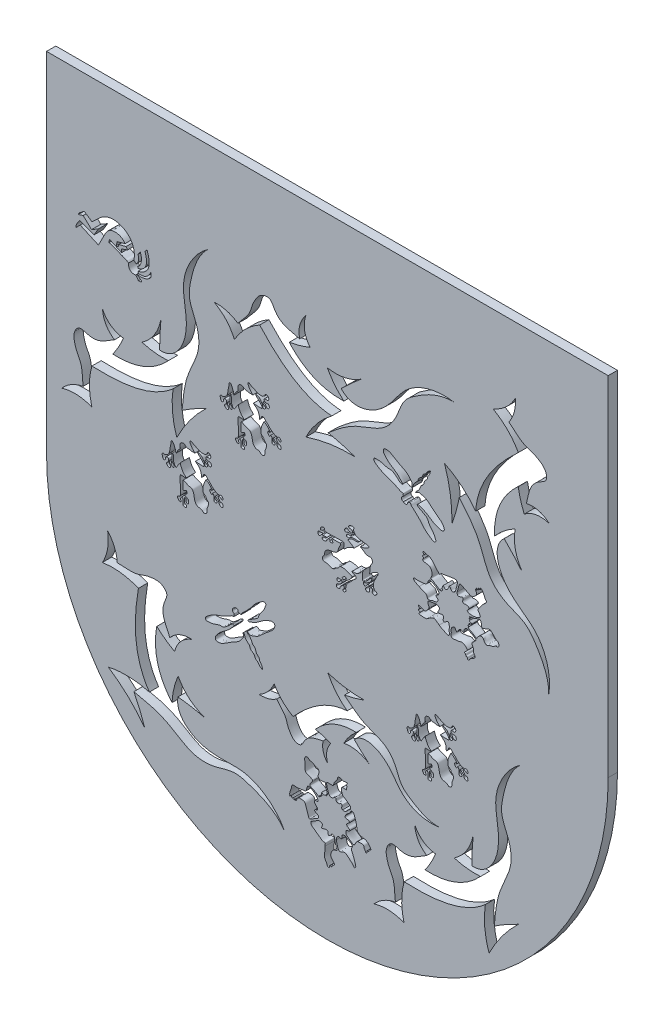
SolidWorks part; units mm, degrees
material "Copper"
ref_plane "Front Plane" through (0, 0, 0) normal (0, 0, 1) x (1, 0, 0)
ref_plane "Top Plane" through (0, 0, 0) normal (0, 1, 0) x (1, 0, 0)
ref_plane "Right Plane" through (0, 0, 0) normal (1, 0, 0) x (0, 0, -1)
sketch "Model" plane through (0, 0, 0) normal (0, 0, 1) x (1, 0, 0)
  line L0 (394.0684, 740.7693) -> (398.6622, 741.3007)
  line L1 (411.6033, 754.0999) -> (411.2957, 759.9449)
  line L2 (405.9947, 783.1893) -> (403.0277, 779.9921)
  line L3 (396.5413, 775.912) -> (393.612, 771.8318)
  line L4 (340.3525, 788.0832) -> (330.4887, 778.9239)
  line L5 (330.4887, 778.9239) -> (319.9202, 785.9695)
  line L6 (311.9939, 778.2193) -> (318.5111, 780.333)
  line L7 (318.5111, 780.333) -> (329.9602, 769.2361)
  line L8 (329.9602, 769.2361) -> (339.2957, 774.7846)
  line L9 (339.2957, 774.7846) -> (333.3069, 764.6565)
  line L10 (333.3069, 764.6565) -> (313.7553, 771.8783)
  line L11 (308.8233, 761.3098) -> (314.4598, 766.9463)
  line L12 (314.4598, 766.9463) -> (339.2957, 755.6733)
  line L13 (339.2957, 755.6733) -> (349.1596, 774.6965)
  line L14 (375.8731, 775.6248) -> (366.0551, 772.786)
  line L15 (366.0551, 772.786) -> (364.9693, 772.786)
  line L16 (364.9693, 772.786) -> (363.6861, 766.9148)
  line L17 (363.6861, 766.9148) -> (366.9435, 767.357)
  line L18 (366.9435, 767.357) -> (366.9435, 770.1209)
  line L19 (366.9435, 770.1209) -> (377.2091, 772.8847)
  line L20 (379.0674, 769.6274) -> (371.0063, 766.9201)
  line L21 (371.0063, 766.9201) -> (371.0063, 762.5101)
  line L22 (1036.7119, 473.4105) -> (1036.7119, 876.6355)
  line L23 (1036.7119, 876.6355) -> (268.3619, 876.6355)
  line L24 (268.3619, 876.6355) -> (268.3619, 473.4105)
  line L25 (268.3619, 473.4105) -> (1036.7119, 473.4105)
  line L26 (1036.7119, 949.6605) -> (268.3619, 949.6605)
  line L27 (268.3619, 949.6605) -> (268.3619, 876.6355)
  line L28 (1036.7119, 876.6355) -> (1036.7119, 949.6605)
  line L29 (384.4445, 760.5081) -> (384.0763, 764.4209)
  line L30 (373.0534, 764.4209) -> (373.0534, 761.3098)
  line L31 (380.6639, 766.7648) -> (373.0534, 764.4209)
  arc A0 (394.0684, 740.7693) -> (390.4794, 745.7939) centre (328.1019, 697.4443) ccw
  arc A1 (393.6582, 749.4855) -> (393.792, 752.0044) centre (388.0165, 751.048) ccw
  arc A2 (393.5074, 755.1974) -> (392.9843, 756.9759) centre (386.3581, 754.0608) ccw
  arc A3 (391.15, 759.2775) -> (387.6746, 761.3098) centre (386.3933, 755.1308) ccw
  arc A4 (355.0412, 770.1209) -> (353.7581, 765.7127) centre (362.1342, 765.6655) ccw
  arc A5 (268.3619, 473.4105) -> (1036.7119, 473.4105) centre (652.5369, 473.4105) ccw
  spline S0 degree 3 poles (855.4392, 698.3823) (844.0962, 713.6317) (829.8955, 725.3892) (812.8372, 733.6549) knots 0.499059 0.499059 0.499059 0.499059 0.500898 0.500898 0.500898 0.500898
  spline S1 degree 3 poles (812.8372, 733.6549) (820.1443, 711.971) (823.5036, 689.6775) (822.9151, 666.7744) knots 0.499152 0.499152 0.499152 0.499152 0.500883 0.500883 0.500883 0.500883
  spline S2 degree 3 poles (822.9151, 666.7744) (827.1929, 678.7461) (830.5522, 690.9617) (832.993, 703.4213) knots 0.499528 0.499528 0.499528 0.499528 0.500373 0.500373 0.500373 0.500373
  spline S3 degree 3 poles (832.993, 703.4213) (842.8567, 691.7291) (862.3877, 668.6155) (871.1795, 627.9534) (898.7, 608.5509) (924.1843, 601.4647) (944.6024, 572.4094) (956.0473, 549.3969) (955.3018, 530.723) knots 0 0 0 0 0.209594 0.407161 0.535059 0.647811 0.757164 1 1 1 1
  spline S4 degree 3 poles (955.3018, 530.723) (959.247, 553.081) (949.6397, 592.8274) (909.5343, 616.9495) (884.1807, 645.3373) (881.8843, 674.5952) (894.3988, 685.4119) knots 0 0 0 0 0.38413 0.579872 0.757798 1 1 1 1
  spline S5 degree 3 poles (894.3988, 685.4119) (903.1222, 676.7447) (911.3753, 667.6494) (919.1583, 658.1259) knots 0.499667 0.499667 0.499667 0.499667 0.500357 0.500357 0.500357 0.500357
  spline S6 degree 3 poles (919.1583, 658.1259) (909.7115, 672.6368) (906.5113, 688.1325) (909.5577, 704.6131) knots 0.498782 0.498782 0.498782 0.498782 0.50096 0.50096 0.50096 0.50096
  spline S7 degree 3 poles (909.5577, 704.6131) (898.7173, 698.7235) (889.2851, 691.1441) (881.2612, 681.8748) knots 0.499295 0.499295 0.499295 0.499295 0.500579 0.500579 0.500579 0.500579
  spline S8 degree 3 poles (881.2612, 681.8748) (880.1178, 711.2872) (890.9027, 736.1819) (913.6159, 756.559) knots 0.498607 0.498607 0.498607 0.498607 0.5017 0.5017 0.5017 0.5017
  spline S9 degree 3 poles (913.6159, 756.559) (915.2717, 746.7779) (918.0248, 737.3154) (921.8752, 728.1715) knots 0.499539 0.499539 0.499539 0.499539 0.500465 0.500465 0.500465 0.500465
  spline S10 degree 3 poles (921.8752, 728.1715) (932.2852, 736.1606) (943.8379, 738.0713) (956.5336, 733.9036) knots 0.498968 0.498968 0.498968 0.498968 0.501122 0.501122 0.501122 0.501122
  spline S11 degree 3 poles (956.5336, 733.9036) (954.7099, 735.3256) (951.1726, 738.0839) (945.2411, 741.017) (939.6264, 742.6548) (934.4156, 743.2451) (929.6214, 743.1617) (926.4462, 742.5859) (924.8297, 742.2928) knots 0 0 0 0 0.203388 0.39451 0.579193 0.715969 0.855401 1 1 1 1
  spline S12 degree 3 poles (924.8297, 742.2928) (925.2108, 743.9218) (925.9826, 747.2202) (927.0309, 752.2207) (928.2759, 757.2089) (929.8877, 762.0557) (932.086, 766.6244) (935.0687, 770.7347) (938.8128, 774.3246) (943.2648, 777.2307) (947.2495, 779.1869) (950.0336, 781.221) (951.6354, 783.0935) (952.4266, 785.453) (952.4919, 788.0258) (952.0106, 790.665) (950.9333, 793.6197) (949.0377, 796.6208) (946.2534, 799.3631) (943.1133, 801.6154) (939.8141, 803.6068) (936.0948, 805.6323) (931.8073, 807.3916) (926.9842, 808.724) (922.1346, 810.4238) (917.5776, 813.0967) (913.2676, 816.3775) (909.1576, 819.9296) (905.1531, 823.5131) (902.3343, 825.6737) (900.9463, 826.7376) knots 0 0 0 0 0.040845 0.082703 0.124739 0.166308 0.207219 0.248003 0.289628 0.333122 0.377274 0.397765 0.416986 0.436378 0.457206 0.479228 0.50152 0.533648 0.564945 0.596348 0.6278 0.659003 0.69968 0.740565 0.781182 0.824711 0.868856 0.913321 0.957319 1 1 1 1
  spline S13 degree 3 poles (900.9463, 826.7376) (907.5632, 836.5492) (910.5256, 847.3969) (909.8334, 859.2808) knots 0.49918 0.49918 0.49918 0.49918 0.500868 0.500868 0.500868 0.500868
  spline S14 degree 3 poles (909.8334, 859.2808) (908.6341, 857.2268) (906.2655, 853.1703) (901.9409, 847.6655) (897.114, 842.7179) (891.7216, 838.3785) (885.8044, 834.5853) (881.5215, 832.6097) (879.3527, 831.6094) knots 0 0 0 0 0.169882 0.335521 0.498998 0.66311 0.829409 1 1 1 1
  spline S15 degree 3 poles (879.3527, 831.6094) (882.0694, 829.9485) (887.4469, 826.6609) (894.7986, 820.7931) (901.7608, 814.0075) (908.268, 806.1584) (911.9399, 800.1017) (913.7887, 797.0524) knots 0 0 0 0 0.193344 0.382711 0.570056 0.783538 1 1 1 1
  spline S16 degree 3 poles (913.7887, 797.0524) (910.619, 794.0802) (904.2416, 788.1003) (895.0787, 778.652) (886.3475, 768.7204) (878.2763, 758.2589) (871.5736, 748.0303) (866.2116, 738.1574) (862.0571, 728.7535) (858.7914, 718.9792) (856.4164, 708.8317) (855.7669, 701.8861) (855.4392, 698.3823) knots 0 0 0 0 0.110893 0.223118 0.335793 0.448248 0.560094 0.647529 0.734746 0.822127 0.91027 1 1 1 1
  spline S17 degree 3 poles (756.6024, 660.2599) (757.4442, 658.4893) (759.5384, 658.5917) (762.3839, 659.8688) (761.7323, 662.8146) (764.2039, 662.7174) (765.6369, 664.0239) (766.6866, 662.6071) (767.1292, 661.035) (768.9106, 659.5483) (771.2993, 657.7826) (773.8896, 654.83) (777.6219, 651.6904) (781.5661, 647.3356) (785.5439, 641.945) (791.2318, 637.7858) (795.5115, 634.7069) (799.4173, 633.3718) (801.4565, 635.418) (800.0957, 638.4359) (798.7207, 642.4097) (794.9624, 647.5334) (791.0103, 651.6568) (789.9314, 656.7955) (785.4827, 659.5707) (780.766, 662.3219) (776.5441, 663.9677) (775.2782, 666.1146) (775.8208, 666.9193) (777.5905, 667.0647) (780.5999, 665.4389) (786.4303, 663.6771) (792.2426, 659.472) (798.1581, 655.3952) (803.6831, 653.3464) (808.1994, 651.6543) (813.1734, 653.262) (811.4897, 660.3783) (804.5383, 665.7458) (795.4754, 672.3131) (788.1882, 679.6452) (781.8398, 680.7151) (778.7291, 682.174) (776.8349, 681.201) (775.1113, 680.5009) (773.9395, 679.3076) (773.1712, 680.0291) knots 0 0 0 0 0.02287 0.030865 0.04383 0.054018 0.062408 0.066972 0.07723 0.088489 0.101131 0.12365 0.148576 0.176512 0.214248 0.251712 0.283384 0.298902 0.308283 0.320402 0.344404 0.375944 0.416788 0.430571 0.453913 0.492135 0.517426 0.52282 0.525816 0.530648 0.548151 0.577862 0.624379 0.657702 0.688663 0.714771 0.732789 0.754604 0.805683 0.870033 0.929204 0.957011 0.969976 0.978366 0.988029 1 1 1 1
  spline S18 degree 3 poles (773.1712, 680.0291) (773.7761, 681.0069) (775.1477, 682.3312) (777.4712, 683.8391) (778.4569, 686.3007) (779.8759, 688.4599) (780.3679, 691.3235) (782.6912, 692.5396) (783.9106, 694.2598) (784.7953, 695.9749) (784.8866, 697.7485) (785.6712, 699.7386) (787.2467, 701.1409) (788.7646, 702.7296) (789.7929, 704.6153) (789.5411, 706.6868) (791.0166, 707.9481) (791.7151, 709.6143) (793.1293, 711.8484) (793.2499, 713.9041) (793.4418, 715.1319) knots 0 0 0 0 0.081648 0.138277 0.193791 0.266989 0.326448 0.389297 0.442066 0.477662 0.526585 0.568162 0.62821 0.675755 0.727172 0.778514 0.811129 0.858756 0.908235 1 1 1 1
  spline S19 degree 3 poles (793.4418, 715.1319) (792.3781, 714.4894) (790.5211, 713.5994) (788.9888, 711.4447) (787.7111, 710.1674) (787.1023, 708.3242) (785.0897, 707.773) (783.7336, 706.1073) (782.8379, 704.1008) (782.1365, 702.1117) (780.5916, 700.632) (778.9846, 699.876) (777.7322, 698.4079) (776.6016, 696.628) (776.3557, 694.0172) (773.8915, 692.4776) (772.4304, 690.3467) (770.5252, 688.5024) (770.0092, 685.781) (769.3028, 684.0101) (768.6269, 683.0801) knots 0 0 0 0 0.091765 0.141244 0.188871 0.221486 0.272828 0.324245 0.37179 0.431838 0.473415 0.522338 0.557934 0.610703 0.673552 0.733011 0.806209 0.861723 0.918352 1 1 1 1
  spline S20 degree 3 poles (768.6269, 683.0801) (767.6682, 683.518) (768.3289, 685.0544) (768.3244, 686.9147) (768.5077, 689.0363) (765.9798, 691.3631) (762.5859, 696.8338) (753.0407, 700.8025) (743.531, 706.7043) (735.9312, 711.1061) (728.7072, 709.9701) (729.1024, 704.7577) (732.3784, 701.2183) (736.3665, 696.8803) (742.3795, 692.9487) (748.4722, 689.1611) (752.3101, 684.4318) (754.9544, 682.262) (755.4898, 680.5689) (754.9504, 679.762) (752.484, 680.1209) (749.3623, 683.4054) (745.0301, 686.7294) (740.7773, 689.7962) (735.6126, 688.8492) (730.2998, 690.9459) (724.1347, 692.4846) (719.9361, 692.2527) (716.6276, 692.3696) (715.5058, 689.7075) (718.2203, 686.5979) (722.6904, 683.8026) (728.6934, 680.1128) (735.1887, 678.472) (740.7126, 676.4702) (745.0316, 674.2044) (748.7451, 672.9248) (751.2837, 671.3824) (753.3342, 670.2965) (754.9569, 670.4821) (756.6656, 670.0469) (755.999, 668.226) (757.0246, 665.9752) (754.0515, 665.4629) (753.9468, 662.3458) (754.6448, 660.3687) (756.6024, 660.2599) knots 0 0 0 0 0.011971 0.021634 0.030024 0.042989 0.070796 0.129967 0.194317 0.245396 0.267211 0.285229 0.311337 0.342298 0.375621 0.422138 0.451849 0.469352 0.474184 0.47718 0.482574 0.507865 0.546087 0.569429 0.583212 0.624056 0.655596 0.679598 0.691717 0.701098 0.716616 0.748288 0.785752 0.823488 0.851424 0.87635 0.898869 0.911511 0.92277 0.933028 0.937592 0.945982 0.95617 0.969135 0.97713 1 1 1 1
  spline S21 degree 3 poles (658.5699, 712.8419) (643.3206, 701.4989) (631.5631, 687.2982) (623.2974, 670.2399) knots 0.499059 0.499059 0.499059 0.499059 0.500898 0.500898 0.500898 0.500898
  spline S22 degree 3 poles (623.2974, 670.2399) (644.9813, 677.547) (667.2748, 680.9063) (690.1779, 680.3178) knots 0.499152 0.499152 0.499152 0.499152 0.500883 0.500883 0.500883 0.500883
  spline S23 degree 3 poles (690.1779, 680.3178) (678.2062, 684.5956) (665.9906, 687.9549) (653.531, 690.3957) knots 0.499528 0.499528 0.499528 0.499528 0.500373 0.500373 0.500373 0.500373
  spline S24 degree 3 poles (653.531, 690.3957) (656.1423, 692.5989) (661.3722, 697.0115) (669.3833, 703.4369) (677.7209, 709.4504) (686.5083, 714.842) (695.8874, 719.2513) (704.5574, 722.4953) (712.1499, 725.3776) (718.5366, 728.07) (724.65, 731.1935) (730.3589, 734.9691) (735.4621, 739.5796) (739.9608, 744.8742) (743.7233, 750.4967) (746.8377, 756.2582) (749.341, 762.0276) (751.6091, 767.8377) (754.0081, 773.5058) (756.863, 778.8483) (760.5568, 783.5978) (764.9376, 787.7418) (769.786, 791.4735) (775.4282, 795.244) (781.694, 799.1541) (788.5929, 803.07) (795.6476, 806.508) (802.9052, 809.3493) (810.415, 811.4344) (818.2268, 812.7189) (823.5362, 812.7094) (826.2293, 812.7045) knots 0 0 0 0 0.046441 0.093012 0.139556 0.186098 0.232927 0.280164 0.3119 0.343319 0.37433 0.405095 0.436065 0.46748 0.499304 0.527852 0.556385 0.584728 0.612637 0.640026 0.666802 0.694016 0.721781 0.749874 0.786231 0.822159 0.857651 0.892821 0.927937 0.963448 1 1 1 1
  spline S25 degree 3 poles (826.2293, 812.7045) (823.4553, 813.0974) (817.8573, 813.8902) (809.3, 813.9009) (800.6934, 813.0911) (792.1628, 811.3806) (783.8539, 808.8044) (775.9065, 805.365) (768.4659, 801.07) (761.8964, 796.1052) (756.2841, 790.5473) (751.4068, 784.71) (746.7988, 778.6126) (742.223, 772.4493) (737.4648, 766.4609) (732.3281, 760.856) (726.7781, 755.7373) (720.732, 751.199) (714.6876, 747.6911) (708.8052, 745.1357) (703.2523, 743.4009) (697.5681, 742.3526) (692.233, 742.1256) (687.3628, 742.6438) (682.9952, 743.7799) (678.8296, 745.653) (674.8858, 748.283) (672.6764, 750.6068) (671.5404, 751.8015) knots 0 0 0 0 0.045817 0.092463 0.139673 0.187153 0.234619 0.281829 0.328618 0.374945 0.416209 0.457635 0.499373 0.541313 0.583303 0.624523 0.665645 0.706728 0.748037 0.779734 0.811541 0.843069 0.874101 0.898603 0.923 0.947648 0.973083 1 1 1 1
  spline S26 degree 3 poles (671.5404, 751.8015) (680.2075, 760.5249) (689.3029, 768.778) (698.8264, 776.561) knots 0.499667 0.499667 0.499667 0.499667 0.500357 0.500357 0.500357 0.500357
  spline S27 degree 3 poles (698.8264, 776.561) (684.3155, 767.1142) (668.8198, 763.914) (652.3392, 766.9604) knots 0.498782 0.498782 0.498782 0.498782 0.50096 0.50096 0.50096 0.50096
  spline S28 degree 3 poles (652.3392, 766.9604) (658.2288, 756.12) (665.8082, 746.6878) (675.0775, 738.6639) knots 0.499295 0.499295 0.499295 0.499295 0.500579 0.500579 0.500579 0.500579
  spline S29 degree 3 poles (675.0775, 738.6639) (645.6651, 737.5205) (620.7703, 748.3054) (600.3933, 771.0186) knots 0.498607 0.498607 0.498607 0.498607 0.5017 0.5017 0.5017 0.5017
  spline S30 degree 3 poles (600.3933, 771.0186) (602.814, 771.4689) (607.6474, 772.3681) (614.7995, 774.2534) (621.8705, 776.5004) (626.4748, 778.351) (628.7808, 779.2779) knots 0 0 0 0 0.249252 0.497679 0.748415 1 1 1 1
  spline S31 degree 3 poles (628.7808, 779.2779) (620.7917, 789.6878) (618.881, 801.2406) (623.0487, 813.9363) knots 0.498968 0.498968 0.498968 0.498968 0.501122 0.501122 0.501122 0.501122
  spline S32 degree 3 poles (623.0487, 813.9363) (614.9554, 804.363) (612.1591, 793.795) (614.6595, 782.2324) knots 0.498846 0.498846 0.498846 0.498846 0.500856 0.500856 0.500856 0.500856
  spline S33 degree 3 poles (614.6595, 782.2324) (606.7878, 784.2083) (592.5669, 785.9568) (580.2246, 798.0668) (575.2316, 811.271) (561.0651, 808.8649) (554.6487, 799.8002) (549.5386, 790.2079) (546.1931, 774.5793) (535.3976, 765.5856) (530.2147, 758.349) knots 0 0 0 0 0.206069 0.324715 0.421259 0.504248 0.61369 0.686644 0.771394 1 1 1 1
  spline S34 degree 3 poles (530.2147, 758.349) (527.8147, 759.825) (523.0765, 762.7389) (516.0019, 765.3322) (509.525, 766.7685) (503.6452, 767.4079) (499.6795, 767.2938) (497.6715, 767.2361) knots 0 0 0 0 0.245664 0.485011 0.653715 0.824659 1 1 1 1
  spline S35 degree 3 poles (497.6715, 767.2361) (510.4233, 760.283) (519.6471, 750.1228) (525.3429, 736.7554) knots 0.499056 0.499056 0.499056 0.499056 0.500947 0.500947 0.500947 0.500947
  spline S36 degree 3 poles (525.3429, 736.7554) (533.8268, 751.5181) (545.3458, 762.9967) (559.8999, 771.1913) knots 0.498959 0.498959 0.498959 0.498959 0.50079 0.50079 0.50079 0.50079
  spline S37 degree 3 poles (559.8999, 771.1913) (585.9574, 742.9265) (618.1758, 715.3276) (658.5699, 712.8419) knots 0 0 0 0 1 1 1 1
  spline S38 degree 3 poles (441.4649, 636.4506) (438.7027, 617.647) (440.4303, 599.2918) (446.6476, 581.385) knots 0.499059 0.499059 0.499059 0.499059 0.500898 0.500898 0.500898 0.500898
  spline S39 degree 3 poles (446.6476, 581.385) (456.8135, 601.8847) (470.202, 620.024) (486.8131, 635.8028) knots 0.499152 0.499152 0.499152 0.499152 0.500883 0.500883 0.500883 0.500883
  spline S40 degree 3 poles (486.8131, 635.8028) (475.323, 630.3624) (464.3098, 624.1) (453.7737, 617.0157) knots 0.499528 0.499528 0.499528 0.499528 0.500373 0.500373 0.500373 0.500373
  spline S41 degree 3 poles (453.7737, 617.0157) (455.0667, 632.258) (457.5999, 662.4122) (480.1356, 697.3815) (474.3954, 730.561) (461.3859, 753.5918) (467.4934, 788.5748) (475.6728, 812.9399) (489.4044, 825.6172) knots 0 0 0 0 0.209594 0.407161 0.535059 0.647811 0.757164 1 1 1 1
  spline S42 degree 3 poles (489.4044, 825.6172) (470.8053, 812.5974) (449.4937, 777.6991) (460.7956, 732.2834) (458.6501, 694.2825) (439.5855, 671.9702) (423.0878, 673.1707) knots 0 0 0 0 0.38413 0.579872 0.757798 1 1 1 1
  spline S43 degree 3 poles (423.0878, 673.1707) (423.0481, 685.4677) (423.6436, 697.7349) (424.8743, 709.9724) knots 0.499667 0.499667 0.499667 0.499667 0.500357 0.500357 0.500357 0.500357
  spline S44 degree 3 poles (424.8743, 709.9724) (424.1161, 706.9165) (422.6299, 700.9266) (418.9513, 692.5387) (414.5869, 685.4467) (409.7146, 679.5434) (404.6059, 674.572) (400.7465, 671.7446) (398.7916, 670.3124) knots 0 0 0 0 0.193794 0.379866 0.561953 0.705377 0.850764 1 1 1 1
  spline S45 degree 3 poles (398.7916, 670.3124) (410.6215, 666.8116) (422.6505, 665.5015) (434.8786, 666.3821) knots 0.499295 0.499295 0.499295 0.499295 0.500579 0.500579 0.500579 0.500579
  spline S46 degree 3 poles (434.8786, 666.3821) (414.8894, 644.7759) (389.6601, 634.7987) (359.1907, 636.4506) knots 0.498607 0.498607 0.498607 0.498607 0.5017 0.5017 0.5017 0.5017
  spline S47 degree 3 poles (359.1907, 636.4506) (360.584, 638.4808) (363.3659, 642.5344) (367.0901, 648.9247) (370.5011, 655.5136) (372.4483, 660.0779) (373.4235, 662.3638) knots 0 0 0 0 0.249252 0.497679 0.748415 1 1 1 1
  spline S48 degree 3 poles (373.4235, 662.3638) (371.4188, 662.7044) (367.5087, 663.3686) (362.0059, 665.411) (356.887, 668.2874) (352.2344, 672.1649) (348.0652, 677.0553) (345.9512, 680.8596) (344.8631, 682.8178) knots 0 0 0 0 0.166107 0.323975 0.477559 0.644562 0.817045 1 1 1 1
  spline S49 degree 3 poles (344.8631, 682.8178) (345.1471, 680.5227) (345.6979, 676.0711) (347.8182, 669.8029) (350.6302, 664.6746) (353.8974, 660.5726) (357.3464, 657.2416) (359.9988, 655.4035) (361.3491, 654.4678) knots 0 0 0 0 0.203388 0.39451 0.579194 0.71597 0.855402 1 1 1 1
  spline S50 degree 3 poles (361.3491, 654.4678) (354.3858, 650.2988) (343.0937, 641.4794) (325.8034, 641.3152) (312.9359, 647.1214) (304.6201, 635.4028) (306.4927, 624.456) (309.6621, 614.0598) (318.3476, 600.6431) (317.0735, 586.65) (318.5257, 577.8681) knots 0 0 0 0 0.206069 0.324715 0.421259 0.504248 0.61369 0.686644 0.771394 1 1 1 1
  spline S51 degree 3 poles (318.5257, 577.8681) (306.909, 575.6092) (297.1438, 570.0334) (289.2301, 561.1407) knots 0.49918 0.49918 0.49918 0.49918 0.500868 0.500868 0.500868 0.500868
  spline S52 degree 3 poles (289.2301, 561.1407) (303.1635, 565.241) (316.87, 564.5789) (330.3497, 559.1543) knots 0.499056 0.499056 0.499056 0.499056 0.500947 0.500947 0.500947 0.500947
  spline S53 degree 3 poles (330.3497, 559.1543) (329.6032, 562.2497) (328.1254, 568.3768) (327.0761, 577.7244) (326.9513, 587.4456) (327.9001, 597.597) (329.5864, 604.4762) (330.4354, 607.9397) knots 0 0 0 0 0.193344 0.382711 0.570057 0.783538 1 1 1 1
  spline S54 degree 3 poles (330.4354, 607.9397) (368.847, 606.3788) (411.1443, 609.6453) (441.4649, 636.4506) knots 0 0 0 0 1 1 1 1
  spline S55 degree 3 poles (398.6622, 741.3007) (398.4257, 741.8358) (397.9684, 742.8701) (396.6946, 743.99) (395.2615, 744.9259) (393.6785, 745.863) (392.8445, 746.8425) (392.4277, 747.332) knots 0 0 0 0 0.196821 0.380507 0.565079 0.782625 1 1 1 1
  spline S56 degree 3 poles (392.4277, 747.332) (399.2913, 746.254) (407.7149, 747.3555) (411.6033, 754.0999) knots 0 0 0 0 1 1 1 1
  spline S57 degree 3 poles (411.2957, 759.9449) (410.0193, 756.305) (405.1809, 749.4227) (397.0049, 749.0541) (393.6582, 749.4855) knots 0 0 0 0 0.533061 1 1 1 1
  spline S58 degree 3 poles (393.792, 752.0044) (399.8073, 752.6889) (412.5827, 762.2294) (407.6953, 777.3765) (405.9947, 783.1893) knots 0 0 0 0 0.47437 1 1 1 1
  spline S59 degree 3 poles (403.0277, 779.9921) (403.402, 778.8189) (404.1766, 776.3908) (405.0075, 772.5986) (405.3487, 768.6633) (404.8914, 764.7443) (403.2433, 761.1564) (400.6031, 758.2529) (397.3086, 756.0479) (394.7671, 755.4792) (393.5074, 755.1974) knots 0 0 0 0 0.119133 0.246548 0.374821 0.49994 0.62392 0.749865 0.876014 1 1 1 1
  spline S60 degree 3 poles (392.9843, 756.9759) (393.7336, 757.5895) (395.2261, 758.8116) (396.7532, 761.3154) (397.744, 764.0691) (398.2748, 767.5514) (398.1262, 771.6448) (397.0621, 774.51) (396.5413, 775.912) knots 0 0 0 0 0.139162 0.277189 0.41746 0.560255 0.784827 1 1 1 1
  spline S61 degree 3 poles (393.612, 771.8318) (393.9197, 770.6136) (394.5424, 768.1486) (394.2735, 764.5943) (393.2166, 761.4417) (391.839, 759.999) (391.15, 759.2775) knots 0 0 0 0 0.277644 0.561767 0.780846 1 1 1 1
  spline S62 degree 3 poles (387.6746, 761.3098) (387.9674, 762.7938) (388.5573, 765.7836) (388.5407, 770.391) (387.8703, 774.958) (386.4658, 779.3532) (384.3136, 783.4167) (381.4366, 786.9964) (377.9965, 790.052) (374.1168, 792.5512) (369.9181, 794.4661) (365.4975, 795.7427) (360.9482, 796.3219) (356.371, 796.1346) (351.8975, 795.1584) (347.6578, 793.4587) (343.7573, 791.0848) (341.4878, 789.0841) (340.3525, 788.0832) knots 0 0 0 0 0.061928 0.124766 0.187869 0.250713 0.313103 0.375422 0.438091 0.501079 0.564057 0.626762 0.689139 0.751391 0.813769 0.876055 0.937996 1 1 1 1
  spline S63 degree 3 poles (319.9202, 785.9695) (318.0889, 785.0168) (316.2963, 782.4975) (312.761, 780.7537) (312.0149, 778.9968) (311.9939, 778.2193) knots 0.000001 0.000001 0.000001 0.000001 0.53037 0.798279 1 1 1 1
  spline S64 degree 3 poles (313.7553, 771.8783) (312.4362, 770.3254) (310.1516, 767.1089) (308.3122, 763.3877) (308.8233, 761.3098) knots 0 0 0 0 0.505243 0.999999 0.999999 0.999999 0.999999
  spline S65 degree 3 poles (349.1596, 774.6965) (349.9011, 775.9058) (351.3362, 778.2462) (354.5494, 780.7914) (358.2183, 782.3143) (362.1943, 782.7617) (366.2139, 782.2665) (370.018, 780.8883) (373.4525, 778.7474) (375.0724, 776.6576) (375.8731, 775.6248) knots 0 0 0 0 0.132212 0.255877 0.377103 0.500628 0.62693 0.753643 0.87824 1 1 1 1
  spline S66 degree 3 poles (377.2091, 772.8847) (377.5634, 772.3865) (378.2914, 771.363) (378.8042, 770.2161) (379.0674, 769.6274) knots 0 0 0 0 0.486685 1 1 1 1
  spline S67 degree 3 poles (371.0063, 762.5101) (369.5145, 763.2202) (366.5307, 764.6403) (362.3428, 766.5443) (358.3615, 768.0656) (356.1482, 769.4356) (355.0412, 770.1209) knots 0 0 0 0 0.279953 0.559931 0.77989 1 1 1 1
  spline S68 degree 3 poles (353.7581, 765.7127) (356.3809, 765.8234) (359.8427, 763.5699) (365.5071, 762.2133) (369.3333, 760.0009) (373.0194, 759.1002) (375.0985, 757.6998) (376.6296, 757.0407) (377.4263, 757.0185) (377.9605, 757.1643) (378.3991, 755.6873) (379.9282, 755.6905) (380.4835, 754.8142) knots 0 0 0 0 0.251875 0.414608 0.592798 0.701894 0.797976 0.851277 0.865807 0.882757 0.897063 1 1 1 1
  spline S69 degree 3 poles (380.4835, 754.8142) (380.425, 753.0287) (380.6606, 749.7379) (384.4215, 745.43) (388.3914, 745.2819) (390.4794, 745.7939) knots 0 0 0 0 0.337832 0.586607 0.999999 0.999999 0.999999 0.999999
  spline S70 degree 3 number of poles 211 (553.5996, 691.043) -> (534.47, 643.1846)
  spline S71 degree 3 number of poles 202 (534.47, 643.1846) -> (553.5996, 691.043)
  spline S72 degree 3 number of poles 211 (717.9194, 548.5843) -> (670.0611, 567.714)
  spline S73 degree 3 number of poles 202 (670.0611, 567.714) -> (717.9194, 548.5843)
  spline S74 degree 3 poles (854.7267, 525.1728) (854.7156, 525.4695) (854.4632, 526.4167) (853.3606, 527.6695) (852.436, 530.1345) (852.647, 533.6418) (851.2938, 536.7161) (849.4872, 540.1347) (852.3065, 541.5707) (853.5083, 543.541) (856.5541, 545.4554) (854.1319, 547.7374) (851.9112, 549.4517) (848.6771, 550.931) (846.0109, 552.4905) (843.8726, 553.0576) (841.9159, 553.113) (840.7583, 551.8324) (839.5128, 550.4813) (839.5436, 548.7276) (839.6793, 547.1841) (838.6204, 545.7358) (837.0104, 546.454) (836.3055, 547.6122) (834.5664, 548.3554) (834.1738, 546.8717) (833.0688, 547.337) (832.8111, 546.2366) (831.9607, 545.8011) (831.4181, 544.9158) (831.4732, 543.8351) (830.6854, 543.1297) (829.5254, 542.0237) (828.9716, 543.4529) (828.0096, 544.0033) (827.9463, 545.2599) (826.82, 546.2532) (825.6144, 546.4648) (825.081, 546.266) knots 0.504555 0.504555 0.504555 0.504555 0.511553 0.525179 0.541676 0.56913 0.600474 0.622434 0.636981 0.659932 0.68115 0.694561 0.720784 0.749249 0.772169 0.789778 0.798757 0.813966 0.825584 0.838885 0.850874 0.860557 0.872175 0.881839 0.894069 0.90074 0.907161 0.912142 0.921202 0.928088 0.934128 0.943867 0.951926 0.961608 0.968252 0.976356 0.986624 1 1 1 1
  spline S75 degree 3 poles (825.081, 546.266) (824.4998, 546.0495) (823.7305, 544.9195) (822.3193, 543.7851) (821.8901, 541.8871) (821.8469, 539.8151) (822.1857, 537.6909) (821.7845, 535.8136) (821.3671, 534.0604) (822.493, 532.7637) (824.2336, 531.5046) (827.2223, 532.3885) (831.1377, 532.1012) (834.4417, 533.5727) (837.7608, 533.8058) (840.074, 532.4883) (842.3443, 531.1175) (843.468, 529.6086) (844.4128, 528.4367) (843.5314, 526.8832) (842.0145, 525.7417) (840.8922, 524.5416) (839.2329, 523.1152) (840.8874, 523.0239) (841.6949, 522.2627) (841.953, 521.2899) (841.9054, 519.8912) (843.2697, 520.2253) (844.2039, 519.3409) (844.0106, 518.157) (844.7009, 516.9367) (845.9969, 517.1891) (846.9815, 518.145) (847.9344, 520.2842) (850.9746, 522.0123) (854.7878, 523.5288) (854.7267, 525.1728) knots 0 0 0 0 0.014572 0.027691 0.040062 0.056022 0.074575 0.087095 0.099487 0.112049 0.122469 0.146161 0.17505 0.210779 0.224879 0.247648 0.268501 0.283047 0.291262 0.298282 0.318986 0.332278 0.342017 0.350665 0.356735 0.367003 0.373536 0.381751 0.390229 0.397964 0.407796 0.415531 0.423406 0.438251 0.465786 0.504555 0.504555 0.504555 0.504555
  spline S76 degree 3 poles (805.4858, 538.5113) (807.418, 537.1345) (810.9488, 535.4477) (814.8409, 533.4538) (817.1973, 532.4149) (818.7685, 532.7858) (820.1409, 534.3398) (818.3799, 538.565) (819.8616, 542.4462) (819.0596, 545.8953) (818.814, 547.2267) (817.9478, 548.5282) (816.1449, 548.4901) (814.8039, 547.2508) (813.597, 545.9784) (811.9864, 545.7523) (810.7317, 546.913) (811.104, 548.4999) (811.3567, 550.0127) (811.5217, 551.9951) (809.8145, 553.1091) (808.1713, 553.0988) (806.7662, 552.4763) (805.3666, 552.1796) (803.852, 552.831) (804.0968, 554.3975) (804.9768, 555.6358) (805.8578, 557.2216) (805.9885, 559.0447) (804.7162, 560.1008) (803.507, 561.3017) (800.748, 561.2807) (797.5971, 561.1224) (794.1617, 560.033) (791.2299, 560.2158) (790.5035, 559.3337) knots 0.478828 0.478828 0.478828 0.478828 0.529291 0.559899 0.572826 0.581694 0.592367 0.611843 0.667376 0.675309 0.685952 0.69655 0.704336 0.720475 0.733793 0.740048 0.753257 0.761371 0.772727 0.787095 0.798671 0.810811 0.820651 0.830686 0.841572 0.847492 0.860854 0.873938 0.886078 0.89489 0.907337 0.920807 0.950162 0.973962 1 1 1 1
  spline S77 degree 3 poles (790.5035, 559.3337) (790.1092, 558.855) (789.797, 557.3309) (790.5553, 555.2794) (791.6446, 553.2833) (791.3723, 550.6409) (789.2863, 548.5666) (787.7778, 546.1877) (785.319, 545.2623) (783.5488, 545.8324) (782.151, 547.1134) (780.2958, 547.1746) (778.9154, 547.8019) (777.3273, 548.4132) (776.8538, 546.749) (778.1455, 546.043) (779.4238, 544.4564) (777.9379, 543.7264) (777.1106, 543.0125) (777.3271, 542.1146) (778.2039, 541.688) (779.2781, 541.0124) (778.8481, 539.6936) (777.5023, 539.247) (778.4016, 537.9869) (780.0025, 537.2444) (782.3281, 537.5134) (784.8715, 536.7597) (786.7517, 537.3774) (788.6091, 537.2663) (789.8389, 538.5832) (791.8766, 539.6664) (794.0447, 541.5891) (796.4695, 542.2704) (798.5437, 543.0118) (801.7465, 541.7252) (803.742, 539.7539) (805.4858, 538.5113) knots 0 0 0 0 0.014132 0.028091 0.046467 0.061075 0.080327 0.106952 0.118855 0.132814 0.143702 0.158049 0.168937 0.178675 0.185476 0.196149 0.207954 0.217111 0.224753 0.229187 0.233812 0.245219 0.25032 0.260205 0.265741 0.276813 0.297845 0.313053 0.331461 0.338472 0.350851 0.36636 0.387989 0.410457 0.419325 0.433284 0.478828 0.478828 0.478828 0.478828
  spline S78 degree 3 poles (778.0075, 570.5143) (780.0661, 569.5118) (783.1112, 568.048) (786.9751, 566.9334) (788.5696, 565.0707) (788.9651, 563.4449) (789.6815, 561.6764) (791.6698, 561.6643) (794.102, 561.7493) (797.1328, 563.5987) (800.7714, 563.2037) (803.1305, 565.0934) (804.7999, 567.7091) (802.7015, 569.4886) (800.807, 570.8467) (801.8783, 572.6611) (804.0536, 573.0392) (805.9135, 576.4543) (804.1487, 578.8232) (802.9883, 579.9226) knots 0.504834 0.504834 0.504834 0.504834 0.576836 0.611293 0.626896 0.650469 0.665272 0.679879 0.706235 0.743178 0.786027 0.811413 0.836772 0.868093 0.88489 0.900027 0.920088 0.952311 1 1 1 1
  spline S79 degree 3 poles (802.9883, 579.9226) (801.7485, 581.0974) (798.7873, 582.8712) (795.3192, 585.0902) (791.8689, 585.4557) (790.213, 583.1203) (789.9388, 580.3318) (787.3314, 577.7918) (782.7443, 577.1396) (777.6605, 576.9374) (773.7802, 576.8379) (770.2967, 577.9115) (770.6189, 574.4087) (773.7729, 572.5891) (776.3519, 571.3204) (778.0075, 570.5143) knots 0 0 0 0 0.050956 0.110768 0.127692 0.151657 0.1886 0.214928 0.257827 0.32988 0.369733 0.392596 0.414598 0.446931 0.504834 0.504834 0.504834 0.504834
  spline S80 degree 3 poles (869.7038, 597.2402) (869.9989, 597.8317) (870.4527, 599.3857) (868.167, 600.9953) (867.6003, 603.597) (866.229, 605.8706) (865.2271, 607.7388) (864.164, 609.4172) (863.1095, 609.9596) (862.2549, 611.362) (861.8913, 610.0527) (862.1493, 609.3433) (861.5981, 607.9983) (860.5154, 609.2671) (859.2677, 609.4883) (858.8867, 608.5833) (859.0642, 607.8874) (859.172, 606.5394) (857.7751, 607.13) (856.6953, 608.4384) (856.7518, 607.1185) (856.7854, 606.4567) (857.0529, 604.9791) (855.8426, 605.8861) (854.6883, 606.9704) (855.7389, 603.8295) (856.6795, 602.448) (856.6734, 599.0698) (853.8973, 597.2253) (851.7764, 594.6572) (848.3769, 594.5954) (845.3134, 596.5605) (840.7507, 598.8559) (837.1629, 600.6709) (834.0365, 601.8126) (832.5837, 600.0078) (832.1257, 596.6866) (830.9486, 593.0503) (830.0921, 590.6529) (829.979, 589.8896) knots 0.500637 0.500637 0.500637 0.500637 0.512936 0.528576 0.548023 0.564246 0.580318 0.590594 0.601293 0.606635 0.613091 0.617263 0.623516 0.633148 0.640335 0.643714 0.650147 0.655827 0.663715 0.671887 0.676813 0.681738 0.688538 0.695805 0.702304 0.711196 0.735999 0.748354 0.770642 0.796876 0.810528 0.833065 0.867216 0.909936 0.918073 0.925213 0.950202 0.984809 1 1 1 1
  spline S81 degree 3 poles (829.979, 589.8896) (829.8443, 588.9798) (829.9625, 587.4889) (831.3194, 585.8209) (832.8892, 586.1453) (834.6215, 586.5171) (836.1549, 587.0883) (838.1859, 587.677) (838.6328, 585.6977) (837.89, 584.3518) (837.0585, 582.4796) (838.1992, 581.7738) (838.8606, 580.7571) (840.6635, 581.1074) (842.7099, 581.0853) (844.8355, 580.5638) (846.8725, 579.0482) (845.6933, 576.8788) (844.4229, 576.0807) (843.6297, 574.7863) (844.9347, 573.4782) (847.8722, 572.4203) (852.5769, 572.3779) (857.3295, 573.2636) (860.2024, 574.5829) (862.2608, 576.3112) (860.9576, 578.5295) (860.3166, 580.6688) (858.77, 581.8248) (858.5138, 584.3854) (862.0878, 587.7038) (864.5078, 593.1341) (868.8196, 595.4672) (869.7038, 597.2402) knots 0 0 0 0 0.018106 0.028257 0.036995 0.047075 0.063324 0.072245 0.080505 0.094365 0.105835 0.112246 0.118123 0.128259 0.14337 0.159759 0.172047 0.185228 0.198483 0.204335 0.210834 0.22963 0.267209 0.300749 0.323829 0.33024 0.34995 0.362456 0.375908 0.384671 0.409299 0.463774 0.500637 0.500637 0.500637 0.500637
  spline S82 degree 3 poles (887.4973, 555.4028) (887.5101, 556.1322) (886.9135, 557.461) (885.5335, 559.2919) (883.388, 560.0423) (881.9827, 561.7452) (880.1219, 563.5083) (877.971, 565.7797) (874.7629, 568.6649) (871.5198, 566.6262) (868.9448, 565.472) (866.5659, 565.267) (864.7837, 564.1112) (863.7227, 565.5261) (863.0755, 567.0196) (863.3183, 569.3941) (862.6167, 571.4656) (861.0311, 573.301) (859.5218, 572.5685) (853.9638, 570.6648) (852.9872, 570.3395) (848.3924, 569.6691) (846.2383, 569.0194) (848.4835, 568.032) (847.3508, 567.2149) (845.821, 566.4065) (848.2693, 565.4997) (846.198, 564.651) (847.871, 563.5405) (849.0909, 563.3992) (849.9618, 562.0947) (849.8496, 561.7075) knots 0.501862 0.501862 0.501862 0.501862 0.519236 0.534137 0.5552 0.570034 0.585574 0.615241 0.648082 0.669845 0.697056 0.714762 0.727938 0.737827 0.750083 0.767263 0.791499 0.802801 0.815778 0.844541 0.893357 0.9094 0.918529 0.930779 0.935723 0.946666 0.957552 0.965495 0.976801 0.986048 1 1 1 1
  spline S83 degree 3 poles (849.8496, 561.7075) (849.7018, 561.1974) (847.9125, 561.4539) (846.5948, 561.1518) (846.0682, 560.2129) (846.1739, 559.13) (845.5451, 558.2858) (844.4433, 558.0221) (845.2298, 557.1834) (846.0573, 556.0467) (843.7065, 556.0551) (845.8455, 555.0947) (846.6183, 553.7616) (849.3522, 553.1094) (851.3215, 551.5458) (853.2641, 550.2013) (854.8325, 549.4379) (855.7081, 548.4708) (856.7241, 548.1472) (857.3994, 549.0595) (857.6377, 550.3173) (858.7949, 551.2714) (859.7475, 552.4692) (860.7765, 553.6533) (862.6761, 553.9711) (864.6828, 553.8824) (866.2543, 552.2749) (866.6108, 550.4075) (867.8499, 549.1519) (868.9372, 547.9646) (870.6621, 546.7448) (872.4139, 548.2132) (874.3536, 548.4849) (876.0242, 549.4154) (877.9714, 549.666) (879.944, 550.1874) (881.3106, 551.4917) (882.9402, 552.4815) (884.8882, 552.1778) (886.8262, 553.2641) (887.4846, 554.6705) (887.4973, 555.4028) knots 0 0 0 0 0.01838 0.026278 0.032103 0.04171 0.05092 0.055388 0.062762 0.07037 0.079847 0.089138 0.102577 0.122255 0.148304 0.162711 0.17796 0.188649 0.193743 0.2001 0.211512 0.224246 0.233456 0.248306 0.259088 0.277737 0.293277 0.307839 0.321334 0.333343 0.347417 0.364207 0.379373 0.393936 0.408238 0.425613 0.440597 0.452438 0.468989 0.484416 0.501862 0.501862 0.501862 0.501862
  spline S84 degree 3 poles (803.0378, 601.6929) (802.1727, 602.3301) (800.9003, 604.5973) (798.2506, 607.0609) (796.4465, 609.918) (793.8982, 611.9965) (791.2216, 613.3042) (788.0742, 613.4991) (786.153, 614.9175) (783.9238, 615.164) (783.0833, 613.517) (784.225, 612.678) (785.0766, 611.2716) (783.7227, 610.4259) (782.0433, 609.4805) (783.5919, 608.4045) (785.2213, 607.0393) (782.9886, 606.6067) (783.0003, 604.986) (783.0984, 603.0162) (785.6582, 603.2571) (788.1525, 602.4044) (791.2794, 602.6285) (793.6081, 600.5119) (795.2167, 598.0363) (795.8046, 594.7702) (795.814, 591.3475) (793.9864, 589.6456) (793.8377, 587.2721) (796.6946, 587.2821) (799.0477, 584.9256) (802.9369, 583.3795) (804.9141, 581.2732) (806.1182, 580.7361) knots 0.499378 0.499378 0.499378 0.499378 0.521286 0.546961 0.570663 0.586302 0.610734 0.627728 0.645895 0.657478 0.665582 0.673268 0.682911 0.690881 0.701289 0.710642 0.720735 0.730309 0.738859 0.750174 0.762058 0.779442 0.805054 0.817361 0.838971 0.86157 0.882271 0.901246 0.908952 0.920647 0.944638 0.97474 1 1 1 1
  spline S85 degree 3 poles (806.1182, 580.7361) (806.8443, 580.4122) (808.4024, 580.0958) (810.4189, 581.9624) (809.4676, 583.811) (809.8305, 585.4264) (809.6154, 586.6939) (810.8276, 588.0528) (812.4045, 586.8614) (813.5659, 584.9034) (817.0875, 585.7438) (817.3991, 588.4687) (818.8939, 589.6903) (818.9967, 591.8554) (821.0675, 590.9853) (821.1756, 588.6295) (823.5945, 586.7113) (826.0498, 587.8288) (827.6574, 589.3488) (828.3563, 591.763) (828.8358, 594.273) (829.8716, 596.9785) (829.9148, 599.5686) (831.0021, 601.2762) (828.8017, 604.6336) (822.9388, 603.4553) (816.9499, 602.7027) (811.873, 601.4474) (807.8487, 601.2322) (805.6649, 598.0432) (804.8247, 600.8343) (803.5752, 601.297) (803.0378, 601.6929) knots 0 0 0 0 0.015233 0.028394 0.043545 0.049728 0.060487 0.067665 0.078923 0.090668 0.111826 0.127669 0.138902 0.150088 0.156772 0.172463 0.194097 0.202187 0.223124 0.235094 0.250576 0.273308 0.290642 0.301548 0.30779 0.362438 0.392828 0.431819 0.462169 0.473018 0.485767 0.499378 0.499378 0.499378 0.499378
  spline S86 degree 3 poles (384.0763, 764.4209) (382.6041, 764.7076) (381.4666, 765.4889) (380.6639, 766.7648) knots 0.499671 0.499671 0.499671 0.499671 0.50034 0.50034 0.50034 0.50034
  spline S87 degree 3 poles (381.2881, 757.0423) (381.9841, 758.5372) (383.0362, 759.6925) (384.4445, 760.5081) knots 0.499674 0.499674 0.499674 0.499674 0.500282 0.500282 0.500282 0.500282
  spline S88 degree 3 poles (373.0534, 761.3098) (374.6221, 761.0851) (375.9232, 759.906) (377.793, 759.1159) (378.1199, 758.5974) (378.3665, 758.3573) (378.408, 757.8502) (379.8718, 758.1057) (380.5737, 757.4885) (381.2881, 757.0423) knots 0 0 0 0 0.457238 0.571818 0.608664 0.647786 0.678886 0.745997 1 1 1 1
  spline S89 degree 3 poles (485.1405, 268.5205) (468.5122, 274.2251) (456.2659, 284.6221) (448.4017, 299.7117) knots 0.498773 0.498773 0.498773 0.498773 0.500967 0.500967 0.500967 0.500967
  spline S90 degree 3 poles (448.4017, 299.7117) (443.4102, 288.2237) (440.6016, 276.264) (439.9759, 263.8325) knots 0.499289 0.499289 0.499289 0.499289 0.500584 0.500584 0.500584 0.500584
  spline S91 degree 3 poles (419.1785, 343.808) (426.6171, 337.0176) (434.7345, 331.1679) (443.5306, 326.2591) knots 0.499536 0.499536 0.499536 0.499536 0.500469 0.500469 0.500469 0.500469
  spline S92 degree 3 poles (443.5306, 326.2591) (446.8654, 339.1578) (454.914, 347.9077) (467.6763, 352.5091) knots 0.49896 0.49896 0.49896 0.49896 0.50113 0.50113 0.50113 0.50113
  spline S93 degree 3 poles (467.6763, 352.5091) (454.9583, 353.0001) (444.7554, 348.6316) (437.0676, 339.4037) knots 0.498837 0.498837 0.498837 0.498837 0.500863 0.500863 0.500863 0.500863
  spline S94 degree 3 poles (437.0676, 339.4037) (433.7281, 346.9365) (426.2378, 359.407) (428.2117, 376.8511) (435.6548, 389.0994) (424.8748, 398.9294) (413.6118, 398.3968) (402.7432, 396.4892) (388.1483, 389.3968) (374.2048, 392.4121) (365.1755, 392.0354) knots 0 0 0 0 0.206069 0.324715 0.421259 0.504248 0.61369 0.686644 0.771394 1 1 1 1
  spline S95 degree 3 poles (365.1755, 392.0354) (364.3365, 404.0212) (359.9259, 414.5517) (351.9439, 423.6268) knots 0.499174 0.499174 0.499174 0.499174 0.500875 0.500875 0.500875 0.500875
  spline S96 degree 3 poles (351.9439, 423.6268) (354.3518, 409.0785) (351.9886, 395.3481) (344.8542, 382.4355) knots 0.499049 0.499049 0.499049 0.499049 0.500955 0.500955 0.500955 0.500955
  spline S97 degree 3 poles (344.8542, 382.4355) (361.9682, 384.8756) (378.352, 382.8348) (394.0055, 376.3129) knots 0.498951 0.498951 0.498951 0.498951 0.500796 0.500796 0.500796 0.500796
  spline S98 degree 3 poles (394.0055, 376.3129) (387.6798, 337.798) (385.738, 294.7702) (408.9985, 260.8989) knots 0 0 0 0 1 1 1 1
  spline S99 degree 3 poles (408.9985, 260.8989) (390.3916, 266.009) (371.6809, 266.5393) (352.8667, 262.4896) knots 0.499052 0.499052 0.499052 0.499052 0.500905 0.500905 0.500905 0.500905
  spline S100 degree 3 poles (352.8667, 262.4896) (372.2668, 249.7088) (388.8894, 233.9725) (402.7347, 215.2809) knots 0.499146 0.499146 0.499146 0.499146 0.50089 0.50089 0.50089 0.50089
  spline S101 degree 3 poles (402.7347, 215.2809) (401.5592, 218.6834) (399.2104, 225.4825) (394.4077, 237.4353) (390.3662, 245.7852) (387.8906, 250.8998) knots 0 0 0 0 0.279617 0.558744 1 1 1 1
  spline S102 degree 3 poles (387.8906, 250.8998) (403.0906, 247.7109) (433.1641, 241.4271) (465.6148, 214.3907) (499.7606, 216.0699) (524.5788, 226.33) (559.0761, 215.8469) (582.6171, 204.5896) (593.6932, 189.1835) knots 0 0 0 0 0.209594 0.407161 0.535059 0.647811 0.757164 1 1 1 1
  spline S103 degree 3 poles (593.6932, 189.1835) (582.8743, 209.5371) (550.3436, 235.3311) (503.179, 229.5614) (465.1503, 236.4254) (445.0248, 258.3979) (448.2759, 274.8743) knots 0 0 0 0 0.38413 0.579872 0.757798 1 1 1 1
  spline S104 degree 3 poles (868.6276, 239.0132) (865.8653, 220.2096) (867.5929, 201.8544) (873.8102, 183.9476) knots 0.499059 0.499059 0.499059 0.499059 0.500898 0.500898 0.500898 0.500898
  spline S105 degree 3 poles (913.9757, 238.3654) (902.4856, 232.925) (891.4725, 226.6626) (880.9363, 219.5783) knots 0.499528 0.499528 0.499528 0.499528 0.500373 0.500373 0.500373 0.500373
  spline S106 degree 3 poles (880.9363, 219.5783) (881.2249, 222.9827) (881.8029, 229.801) (882.9241, 240.0091) (884.5674, 250.1568) (886.9687, 260.1829) (890.4828, 269.9328) (894.3196, 278.3573) (897.6502, 285.764) (900.2624, 292.184) (902.3767, 298.7154) (903.7437, 305.422) (904.0921, 312.2906) (903.5293, 319.2155) (902.2141, 325.8518) (900.3423, 332.1279) (898.0329, 337.9776) (895.5282, 343.6898) (893.2167, 349.394) (891.4576, 355.1905) (890.7112, 361.1607) (890.8786, 367.1888) (891.6682, 373.2558) (892.9917, 379.9116) (894.6575, 387.1071) (896.7667, 394.7542) (899.3242, 402.1736) (902.447, 409.3147) (906.2828, 416.0993) (910.8983, 422.5314) (914.6593, 426.279) (916.567, 428.1798) knots 0 0 0 0 0.046441 0.093012 0.139556 0.186098 0.232927 0.280164 0.3119 0.343319 0.37433 0.405094 0.436065 0.46748 0.499304 0.527852 0.556385 0.584728 0.612637 0.640026 0.666802 0.694016 0.721781 0.749874 0.786231 0.822159 0.857651 0.892821 0.927937 0.963448 1 1 1 1
  spline S107 degree 3 poles (916.567, 428.1798) (897.9679, 415.16) (876.6564, 380.2617) (887.9582, 334.846) (885.8128, 296.8451) (866.7481, 274.5328) (850.2504, 275.7334) knots 0 0 0 0 0.38413 0.579872 0.757798 1 1 1 1
  spline S108 degree 3 poles (850.2504, 275.7334) (850.2107, 288.0303) (850.8062, 300.2975) (852.0369, 312.535) knots 0.499667 0.499667 0.499667 0.499667 0.500357 0.500357 0.500357 0.500357
  spline S109 degree 3 poles (579.7442, 356.0556) (575.4724, 346.0301) (568.5545, 338.41) (558.9907, 333.1952) knots 0.49918 0.49918 0.49918 0.49918 0.500817 0.500817 0.500817 0.500817
  spline S110 degree 3 poles (558.9907, 333.1952) (567.9036, 332.676) (576.0394, 334.8978) (583.3981, 339.8605) knots 0.499248 0.499248 0.499248 0.499248 0.50071 0.50071 0.50071 0.50071
  spline S111 degree 3 poles (709.8568, 326.2015) (702.7142, 332.0387) (695.8927, 338.2286) (689.3924, 344.7711) knots 0.499691 0.499691 0.499691 0.499691 0.500289 0.500289 0.500289 0.500289
  spline S112 degree 3 poles (689.3924, 344.7711) (697.5049, 354.157) (719.4483, 352.4346) (740.7392, 333.4195) (758.8308, 303.3404) (788.6405, 296.1349) (805.409, 299.0938) knots 0 0 0 0 0.242202 0.420128 0.61587 1 1 1 1
  spline S113 degree 3 poles (805.409, 299.0938) (791.4036, 298.5347) (774.1443, 307.1184) (752.3527, 322.432) (747.0381, 341.5452) (732.4862, 362.1856) (701.9896, 368.7794) (684.6545, 383.4277) (675.8853, 390.8255) knots 0 0 0 0 0.242836 0.352189 0.464941 0.592839 0.790406 1 1 1 1
  spline S114 degree 3 poles (675.8853, 390.8255) (685.23, 392.656) (694.3917, 395.1755) (703.3704, 398.3839) knots 0.499677 0.499677 0.499677 0.499677 0.500408 0.500408 0.500408 0.500408
  spline S115 degree 3 poles (703.3704, 398.3839) (686.1931, 397.9425) (669.473, 400.462) (653.2101, 405.9423) knots 0.499235 0.499235 0.499235 0.499235 0.500734 0.500734 0.500734 0.500734
  spline S116 degree 3 poles (653.2101, 405.9423) (659.4093, 393.1486) (668.2275, 382.4981) (679.6645, 373.9908) knots 0.499222 0.499222 0.499222 0.499222 0.500815 0.500815 0.500815 0.500815
  spline S117 degree 3 poles (679.6645, 373.9908) (649.3689, 372.1265) (625.2051, 351.4273) (605.662, 330.2287) knots 0 0 0 0 1 1 1 1
  spline S118 degree 3 poles (525.0093, 418.1793) (523.0575, 417.9939) (522.4375, 415.991) (522.6644, 412.8803) (525.6553, 412.485) (524.7187, 410.1958) (525.4562, 408.4024) (523.7659, 407.9005) (522.1372, 408.0223) (520.1309, 406.8569) (517.6547, 405.2161) (513.9943, 403.7919) (509.7674, 401.3584) (504.3263, 399.1415) (497.9003, 397.2473) (492.0466, 393.3249) (487.6896, 390.3564) (485.0991, 387.1428) (486.3245, 384.5268) (489.6258, 384.7732) (493.8303, 384.7062) (499.9303, 386.4855) (505.1567, 388.7889) (510.3546, 388.0452) (514.4839, 391.2765) (518.6824, 394.7678) (521.6729, 398.1721) (524.1233, 398.6274) (524.694, 397.8423) (524.2253, 396.1296) (521.6682, 393.8577) (518.0187, 388.9816) (512.0792, 384.958) (506.225, 380.7936) (502.4102, 376.3025) (499.2755, 372.6373) (499.0849, 367.4134) (506.3479, 366.5617) (513.7692, 371.2581) (523.0402, 377.5282) (532.4225, 381.8683) (535.5992, 387.4679) (538.0339, 389.892) (537.7676, 392.0047) (537.6991, 393.8638) (536.9786, 395.3731) (537.9194, 395.8483) knots 0 0 0 0 0.02287 0.030865 0.04383 0.054018 0.062408 0.066972 0.07723 0.088489 0.101131 0.12365 0.148576 0.176512 0.214248 0.251712 0.283384 0.298902 0.308283 0.320402 0.344404 0.375944 0.416788 0.430571 0.453913 0.492135 0.517426 0.52282 0.525816 0.530648 0.548151 0.577862 0.624379 0.657702 0.688663 0.714771 0.732789 0.754604 0.805683 0.870033 0.929204 0.957011 0.969976 0.978366 0.988029 1 1 1 1
  spline S119 degree 3 poles (537.9194, 395.8483) (538.6313, 394.9455) (539.4066, 393.2037) (540.0289, 390.5046) (542.0049, 388.7364) (543.5485, 386.6644) (546.0712, 385.2227) (546.4193, 382.6235) (547.6188, 380.8894) (548.9279, 379.4714) (550.5632, 378.7791) (552.165, 377.3611) (552.9438, 375.401) (553.9175, 373.4312) (555.3379, 371.82) (557.3706, 371.3481) (558.0512, 369.5303) (559.378, 368.304) (560.9936, 366.211) (562.8841, 365.3945) (563.9722, 364.7943) knots 0 0 0 0 0.081648 0.138277 0.193791 0.266989 0.326448 0.389297 0.442066 0.477662 0.526585 0.568162 0.62821 0.675755 0.727172 0.778514 0.811129 0.858756 0.908235 1 1 1 1
  spline S120 degree 3 poles (563.9722, 364.7943) (563.7323, 366.0136) (563.5311, 368.063) (562.0304, 370.2399) (561.2671, 371.8774) (559.7433, 373.0799) (559.9137, 375.1596) (558.8123, 377.0036) (557.2332, 378.5316) (555.6039, 379.871) (554.7418, 381.8288) (554.5811, 383.5974) (553.6298, 385.2765) (552.3439, 386.9476) (549.9747, 388.0716) (549.3708, 390.9138) (547.8681, 393.0156) (546.7867, 395.4367) (544.4058, 396.8523) (542.9834, 398.1218) (542.3406, 399.0751) knots 0 0 0 0 0.091765 0.141244 0.188871 0.221486 0.272828 0.324245 0.37179 0.431838 0.473415 0.522338 0.557934 0.610703 0.673552 0.733011 0.806209 0.861723 0.918352 1 1 1 1
  spline S121 degree 3 poles (542.3406, 399.0751) (543.08, 399.8262) (544.2977, 398.6798) (546.0474, 398.0478) (547.9783, 397.1499) (551.0294, 398.7296) (557.331, 400.0477) (564.325, 407.6598) (573.1234, 414.5776) (579.859, 420.2135) (581.2623, 427.3904) (576.2291, 428.8017) (571.7826, 426.9338) (566.3422, 424.67) (560.5912, 420.3643) (554.9482, 415.9345) (549.1915, 413.9455) (546.2481, 412.2029) (544.474, 412.2787) (543.9003, 413.0616) (545.0811, 415.2565) (549.2351, 417.0666) (553.8403, 420.0006) (558.1768, 422.9481) (559.0534, 428.1252) (562.8407, 432.4004) (566.3951, 437.6675) (567.6133, 441.6922) (568.8546, 444.7612) (566.7367, 446.7258) (562.8863, 445.2385) (558.7307, 441.9942) (553.2103, 437.6152) (549.4469, 432.0727) (545.6766, 427.5666) (542.0702, 424.283) (539.5977, 421.2311) (537.2801, 419.3731) (535.5583, 417.8177) (535.1777, 416.2294) (534.1844, 414.7726) (532.7013, 416.0218) (530.2354, 415.8278) (530.7709, 418.7969) (527.8776, 419.9614) (525.781, 419.9816) (525.0093, 418.1793) knots 0 0 0 0 0.011971 0.021634 0.030024 0.042989 0.070796 0.129967 0.194317 0.245396 0.267211 0.285229 0.311337 0.342298 0.375621 0.422138 0.451849 0.469352 0.474184 0.47718 0.482574 0.507865 0.546087 0.569429 0.583212 0.624056 0.655596 0.679598 0.691717 0.701098 0.716616 0.748288 0.785752 0.823488 0.851424 0.87635 0.898869 0.911511 0.92277 0.933028 0.937592 0.945982 0.95617 0.969135 0.97713 1 1 1 1
  spline S122 degree 3 number of poles 211 (809.3409, 426.0832) -> (790.2113, 378.2248)
  spline S123 degree 3 number of poles 202 (790.2113, 378.2248) -> (809.3409, 426.0832)
  spline S124 degree 3 poles (649.5722, 198.5996) (649.7333, 197.5374) (649.0299, 195.0346) (649.1615, 191.4189) (648.4169, 188.1229) (648.7491, 184.8512) (649.717, 182.034) (651.8048, 179.6705) (652.1604, 177.3091) (653.5623, 175.5585) (655.3212, 176.1288) (655.1072, 177.5294) (655.4995, 179.126) (657.0548, 178.7667) (658.9109, 178.2477) (658.5767, 180.1035) (658.3898, 182.221) (660.2745, 180.9481) (661.4123, 182.1025) (662.7358, 183.5646) (660.7553, 185.2043) (659.5945, 187.5711) (657.225, 189.6237) (657.0751, 192.767) (657.6881, 195.6549) (659.5819, 198.3801) (661.9955, 200.8069) (664.4912, 200.7181) (666.2746, 202.2913) (664.2475, 204.3043) (664.2499, 207.6345) (662.5931, 211.4779) (662.6843, 214.3653) (662.2127, 215.5966) knots 0.499378 0.499378 0.499378 0.499378 0.521286 0.546961 0.570663 0.586302 0.610734 0.627728 0.645895 0.657478 0.665582 0.673268 0.682911 0.690881 0.701289 0.710642 0.720735 0.730309 0.738859 0.750174 0.762058 0.779442 0.805054 0.817361 0.838971 0.86157 0.882271 0.901246 0.908952 0.920647 0.944638 0.97474 1 1 1 1
  spline S125 degree 3 poles (662.2127, 215.5966) (661.9283, 216.339) (661.0503, 217.6645) (658.3045, 217.7705) (657.67, 215.7906) (656.2712, 214.905) (655.527, 213.8567) (653.709, 213.7529) (653.4364, 215.7103) (653.9996, 217.9161) (650.9153, 219.812) (648.7681, 218.1056) (646.8473, 218.2987) (645.2437, 216.8405) (644.3947, 218.92) (645.9841, 220.6622) (645.63, 223.7291) (643.1036, 224.675) (640.8921, 224.7369) (638.6907, 223.5241) (636.5769, 222.0883) (633.9314, 220.9076) (632.0694, 219.1067) (630.0931, 218.6681) (629.2749, 214.7381) (634.2539, 211.4256) (639.0208, 207.7229) (643.4984, 205.0207) (646.4961, 202.3273) (650.2953, 203.038) (648.9157, 200.4704) (649.4721, 199.2596) (649.5722, 198.5996) knots 0 0 0 0 0.015233 0.028394 0.043545 0.049728 0.060487 0.067665 0.078923 0.090668 0.111826 0.127669 0.138902 0.150088 0.156772 0.172463 0.194097 0.202187 0.223124 0.235094 0.250576 0.273308 0.290642 0.301548 0.30779 0.362438 0.392828 0.431819 0.462169 0.473018 0.485767 0.499378 0.499378 0.499378 0.499378
  spline S126 degree 3 poles (689.3179, 202.9472) (688.5711, 205.1117) (687.4529, 208.3) (685.5089, 211.8203) (685.6985, 214.2649) (686.5685, 215.6942) (687.3125, 217.4513) (685.9151, 218.8658) (684.1351, 220.5255) (680.6843, 221.3609) (678.3908, 224.2131) (675.3864, 224.545) (672.3563, 223.8758) (672.5819, 221.1338) (672.9612, 218.8339) (670.9206, 218.3084) (669.1151, 219.5791) (665.3851, 218.4795) (664.958, 215.5565) (665.0011, 213.9586) knots 0.504834 0.504834 0.504834 0.504834 0.576836 0.611293 0.626896 0.650469 0.665272 0.679879 0.706235 0.743178 0.786027 0.811413 0.836772 0.868093 0.88489 0.900027 0.920088 0.952311 1 1 1 1
  spline S127 degree 3 poles (665.0011, 213.9586) (665.0471, 212.2512) (665.8866, 208.9031) (666.7699, 204.8817) (668.9512, 202.1835) (671.7735, 202.6639) (673.9391, 204.4419) (677.5789, 204.3941) (681.2836, 201.6118) (685.0214, 198.16) (687.8356, 195.4865) (689.5396, 192.2642) (691.7886, 194.9689) (690.8451, 198.4857) (689.9185, 201.2066) (689.3179, 202.9472) knots 0 0 0 0 0.050956 0.110768 0.127692 0.151657 0.1886 0.214928 0.257827 0.32988 0.369733 0.392596 0.414598 0.446931 0.504834 0.504834 0.504834 0.504834
  spline S128 degree 3 poles (692.5173, 245.0068) (692.1246, 247.3466) (690.8207, 251.036) (689.4785, 255.1981) (688.5469, 257.5989) (687.1736, 258.4477) (685.1043, 258.3193) (683.3619, 254.0864) (679.5697, 252.3897) (677.6978, 249.3837) (676.9301, 248.2685) (676.6224, 246.7358) (677.9241, 245.4879) (679.7487, 245.4159) (681.5018, 245.4623) (682.8005, 244.4833) (682.867, 242.7753) (681.4817, 241.9165) (680.2333, 241.0254) (678.7148, 239.7404) (679.1343, 237.7454) (680.3034, 236.5908) (681.7371, 236.0375) (682.9367, 235.2575) (683.547, 233.726) (682.2663, 232.7914) (680.7683, 232.538) (679.0241, 232.0397) (677.6426, 230.8429) (677.7955, 229.1965) (677.8013, 227.4924) (679.767, 225.5563) (682.107, 223.4402) (685.3066, 221.7813) (687.2503, 219.579) (688.3877, 219.689) knots 0.478828 0.478828 0.478828 0.478828 0.529291 0.559899 0.572826 0.581694 0.592367 0.611843 0.667376 0.675309 0.685952 0.69655 0.704336 0.720475 0.733793 0.740048 0.753257 0.761371 0.772727 0.787095 0.798671 0.810811 0.820651 0.830686 0.841572 0.847492 0.860854 0.873938 0.886078 0.89489 0.907337 0.920807 0.950162 0.973962 1 1 1 1
  spline S129 degree 3 poles (688.3877, 219.689) (689.005, 219.7488) (690.3035, 220.6057) (691.2179, 222.5925) (691.8591, 224.7742) (693.9201, 226.4501) (696.8619, 226.4419) (699.6107, 227.0573) (702.0037, 225.973) (702.8523, 224.3182) (702.9349, 222.424) (704.2034, 221.069) (704.736, 219.6493) (705.4266, 218.094) (706.9383, 218.936) (706.5241, 220.3486) (706.7421, 222.3744) (708.309, 221.8399) (709.3987, 221.7597) (709.8806, 222.5477) (709.5623, 223.4693) (709.2804, 224.7067) (710.517, 225.3351) (711.7844, 224.6992) (712.0395, 226.2262) (711.4326, 227.8832) (709.5978, 229.3375) (708.3324, 231.6689) (706.5662, 232.5616) (705.3313, 233.9535) (703.5305, 233.8919) (701.3236, 234.5669) (698.4311, 234.7404) (696.2348, 235.9733) (694.2437, 236.9157) (692.8889, 240.0902) (692.8717, 242.8951) (692.5173, 245.0068) knots 0 0 0 0 0.014132 0.028091 0.046467 0.061075 0.080327 0.106952 0.118855 0.132814 0.143702 0.158049 0.168937 0.178675 0.185476 0.196149 0.207954 0.217111 0.224753 0.229187 0.233812 0.245219 0.25032 0.260205 0.265741 0.276813 0.297845 0.313053 0.331461 0.338472 0.350851 0.36636 0.387989 0.410457 0.419325 0.433284 0.478828 0.478828 0.478828 0.478828
  spline S130 degree 3 poles (667.1305, 289.2571) (666.9285, 289.0395) (666.4373, 288.1912) (666.331, 286.5257) (665.2418, 284.1289) (662.6126, 281.7981) (661.3956, 278.6673) (660.2557, 274.9726) (657.2468, 275.9507) (655.0038, 275.4073) (651.4964, 276.2074) (651.5955, 272.881) (651.9536, 270.0984) (653.1944, 266.7656) (653.9769, 263.7776) (655.0879, 261.8646) (656.4324, 260.4418) (658.1565, 260.5288) (659.9925, 260.6034) (661.2108, 261.8653) (662.2063, 263.0527) (663.9791, 263.328) (664.6097, 261.6817) (664.2892, 260.3643) (664.9934, 258.6091) (666.3201, 259.3806) (666.7725, 258.2703) (667.7328, 258.8661) (668.6421, 258.5727) (669.6517, 258.815) (670.3769, 259.6182) (671.4328, 259.5599) (673.0352, 259.5217) (672.4161, 258.1196) (672.7072, 257.0501) (671.8634, 256.1168) (671.9574, 254.618) (672.6602, 253.6159) (673.178, 253.3793) knots 0.504555 0.504555 0.504555 0.504555 0.511553 0.525179 0.541676 0.56913 0.600474 0.622434 0.636981 0.659932 0.68115 0.694561 0.720784 0.749249 0.772169 0.789778 0.798757 0.813966 0.825584 0.838885 0.850874 0.860557 0.872175 0.881839 0.894069 0.90074 0.907161 0.912142 0.921202 0.928088 0.934128 0.943867 0.951926 0.961608 0.968252 0.976356 0.986624 1 1 1 1
  spline S131 degree 3 poles (673.178, 253.3793) (673.7421, 253.1215) (675.0851, 253.3764) (676.8852, 253.1808) (678.5307, 254.2193) (680.0264, 255.6539) (681.2888, 257.3955) (682.9, 258.4393) (684.4348, 259.3839) (684.5555, 261.0969) (684.2151, 263.218) (681.4768, 264.7063) (678.9113, 267.6781) (675.5345, 268.9739) (673.0227, 271.1559) (672.3187, 273.7232) (671.6827, 276.2979) (671.955, 278.1594) (672.1156, 279.6562) (673.8373, 280.1314) (675.7171, 279.866) (677.3593, 279.921) (679.5412, 279.7563) (678.4358, 280.9908) (678.4031, 282.1) (678.9084, 282.9704) (679.9312, 283.9257) (678.7302, 284.6542) (678.695, 285.9402) (679.6689, 286.6406) (680.0436, 287.9917) (678.9487, 288.7296) (677.5766, 288.7498) (675.3901, 287.911) (672.0184, 288.8388) (668.2497, 290.4628) (667.1305, 289.2571) knots 0 0 0 0 0.014572 0.027691 0.040062 0.056022 0.074575 0.087095 0.099487 0.112049 0.122469 0.146161 0.17505 0.210779 0.224879 0.247648 0.268501 0.283047 0.291262 0.298282 0.318986 0.332278 0.342017 0.350665 0.356735 0.367003 0.373536 0.381751 0.390229 0.397964 0.407796 0.415531 0.423406 0.438251 0.465786 0.504555 0.504555 0.504555 0.504555
  spline S132 degree 3 poles (622.5823, 291.0536) (622.0576, 290.5469) (621.5397, 289.1854) (621.2209, 286.915) (622.2075, 284.8673) (621.9969, 282.6695) (622.0661, 280.107) (621.9808, 276.9799) (622.2092, 272.6713) (625.944, 271.8197) (628.5809, 270.815) (630.408, 269.2778) (632.4854, 268.8349) (632.2353, 267.0841) (631.6368, 265.5705) (629.7861, 264.0631) (628.8175, 262.1022) (628.6409, 259.6833) (630.226, 259.134) (635.5022, 256.55) (636.4228, 256.0894) (640.1459, 253.3145) (642.1284, 252.2507) (641.239, 254.5365) (642.6178, 254.3133) (644.2711, 253.8032) (643.1812, 256.1756) (645.2458, 255.3111) (644.8481, 257.2794) (644.0854, 258.2419) (644.392, 259.7801) (644.7452, 259.9746) knots 0.501862 0.501862 0.501862 0.501862 0.519236 0.534137 0.5552 0.570034 0.585574 0.615241 0.648082 0.669845 0.697056 0.714762 0.727938 0.737827 0.750083 0.767263 0.791499 0.802801 0.815778 0.844541 0.893357 0.9094 0.918529 0.930779 0.935723 0.946666 0.957552 0.965495 0.976801 0.986048 1 1 1 1
  spline S133 degree 3 poles (644.7452, 259.9746) (645.2104, 260.2308) (646.2942, 258.7842) (647.4396, 258.066) (648.4759, 258.3575) (649.1669, 259.198) (650.2084, 259.3503) (651.174, 258.7577) (651.2109, 259.9069) (651.4296, 261.2958) (653.0858, 259.6275) (652.2525, 261.8192) (652.6486, 263.3083) (651.1767, 265.7026) (650.8898, 268.2008) (650.4668, 270.5251) (649.8976, 272.1739) (649.9624, 273.4769) (649.4728, 274.4242) (648.3502, 274.2566) (647.2923, 273.5357) (645.7993, 273.6793) (644.2788, 273.5059) (642.7139, 273.3962) (641.146, 274.5147) (639.7897, 275.9964) (639.8151, 278.2443) (640.8835, 279.8168) (640.8952, 281.5809) (640.9659, 283.1893) (640.6087, 285.2714) (638.3317, 285.4719) (636.768, 286.6513) (634.9288, 287.1746) (633.3747, 288.3743) (631.6112, 289.4004) (629.7226, 289.4445) (627.8704, 289.8969) (626.7077, 291.4892) (624.5692, 292.0913) (623.1091, 291.5624) (622.5823, 291.0536) knots 0 0 0 0 0.01838 0.026278 0.032103 0.04171 0.05092 0.055388 0.062762 0.07037 0.079847 0.089138 0.102577 0.122255 0.148304 0.162711 0.17796 0.188649 0.193743 0.2001 0.211512 0.224246 0.233456 0.248306 0.259088 0.277737 0.293277 0.307839 0.321334 0.333343 0.347417 0.364207 0.379373 0.393936 0.408238 0.425613 0.440597 0.452438 0.468989 0.484416 0.501862 0.501862 0.501862 0.501862
  spline S134 degree 3 poles (605.5807, 248.8882) (604.9538, 248.6786) (603.5341, 247.9007) (604.0122, 245.1462) (602.5732, 242.9058) (601.9352, 240.3286) (601.3226, 238.299) (600.8875, 236.3605) (601.2496, 235.2314) (600.8623, 233.6354) (602.0452, 234.3041) (602.3644, 234.9882) (603.7052, 235.5495) (603.5736, 233.8867) (604.2995, 232.848) (605.2088, 233.2186) (605.5753, 233.8361) (606.4523, 234.8655) (607.0224, 233.4602) (606.8608, 231.7715) (607.7542, 232.7447) (608.1983, 233.2365) (609.054, 234.4705) (609.2685, 232.9733) (609.3181, 231.3903) (610.796, 234.3542) (611.1078, 235.9962) (613.5009, 238.3806) (616.7682, 237.7218) (620.0837, 238.0381) (622.5313, 235.678) (623.308, 232.1222) (624.9112, 227.2728) (626.1647, 223.4524) (627.5682, 220.4344) (629.8716, 220.6833) (632.5439, 222.7079) (635.9475, 224.4468) (638.2483, 225.5364) (638.868, 225.9962) knots 0.500637 0.500637 0.500637 0.500637 0.512936 0.528576 0.548023 0.564246 0.580318 0.590594 0.601293 0.606635 0.613091 0.617263 0.623516 0.633148 0.640335 0.643714 0.650147 0.655827 0.663715 0.671887 0.676813 0.681738 0.688538 0.695805 0.702304 0.711196 0.735999 0.748354 0.770642 0.796876 0.810528 0.833065 0.867216 0.909936 0.918073 0.925213 0.950202 0.984809 1 1 1 1
  spline S135 degree 3 poles (638.868, 225.9962) (639.6067, 226.5443) (640.5772, 227.6821) (640.7972, 229.821) (639.4579, 230.7016) (637.97, 231.6637) (636.4818, 232.344) (634.6294, 233.3639) (635.713, 235.0795) (637.19, 235.5059) (639.1017, 236.2418) (638.7942, 237.5475) (639.0455, 238.734) (637.5229, 239.7612) (636.0916, 241.2239) (634.9573, 243.0956) (634.5886, 245.6077) (636.9564, 246.3079) (638.4191, 245.9739) (639.8952, 246.3283) (639.8973, 248.1761) (638.5683, 251.0013) (635.2716, 254.358) (631.2847, 257.0922) (628.3204, 258.1909) (625.6428, 258.4242) (624.9957, 255.9341) (623.9362, 253.9682) (624.2125, 252.0572) (622.583, 250.0653) (617.7093, 250.2462) (612.1583, 248.1175) (607.4596, 249.5166) (605.5807, 248.8882) knots 0 0 0 0 0.018106 0.028257 0.036995 0.047075 0.063324 0.072245 0.080505 0.094365 0.105835 0.112246 0.118123 0.128259 0.14337 0.159759 0.172047 0.185228 0.198483 0.204335 0.210834 0.22963 0.267209 0.300749 0.323829 0.33024 0.34995 0.362456 0.375908 0.384671 0.409299 0.463774 0.500637 0.500637 0.500637 0.500637
  spline S136 degree 3 poles (605.662, 330.2287) (594.7464, 336.3747) (586.1072, 344.9837) (579.7442, 356.0556) knots 0.499315 0.499315 0.499315 0.499315 0.500901 0.500901 0.500901 0.500901
  spline S137 degree 3 poles (583.3981, 339.8605) (587.2853, 334.4331) (595.3819, 327.6878) (597.891, 315.9663) (601.7236, 308.7721) (606.5359, 301.9735) (617.1607, 300.1689) (620.9055, 310.0722) (630.1622, 319.1547) (640.8279, 320.466) (646.7317, 321.9479) knots 0 0 0 0 0.228606 0.313356 0.38631 0.495752 0.578741 0.675285 0.793931 1 1 1 1
  spline S138 degree 3 poles (646.7317, 321.9479) (644.8564, 313.276) (646.9536, 305.35) (653.0236, 298.17) knots 0.499258 0.499258 0.499258 0.499258 0.500999 0.500999 0.500999 0.500999
  spline S139 degree 3 poles (653.0236, 298.17) (649.8978, 307.6917) (651.3309, 316.3563) (657.3226, 324.1638) knots 0.499029 0.499029 0.499029 0.499029 0.500894 0.500894 0.500894 0.500894
  spline S140 degree 3 poles (657.3226, 324.1638) (650.4647, 327.0516) (643.3679, 329.1164) (636.032, 330.3583) knots 0.499597 0.499597 0.499597 0.499597 0.500399 0.500399 0.500399 0.500399
  spline S141 degree 3 poles (636.032, 330.3583) (651.3148, 347.3932) (669.9859, 355.4819) (692.0452, 354.6243) knots 0.498528 0.498528 0.498528 0.498528 0.501206 0.501206 0.501206 0.501206
  spline S142 degree 3 poles (692.0452, 354.6243) (685.0932, 348.6063) (679.4087, 341.5322) (674.9915, 333.4019) knots 0.499498 0.499498 0.499498 0.499498 0.500611 0.500611 0.500611 0.500611
  spline S143 degree 3 poles (674.9915, 333.4019) (687.3519, 335.6867) (698.9737, 333.2866) (709.8568, 326.2015) knots 0.499169 0.499169 0.499169 0.499169 0.501055 0.501055 0.501055 0.501055
  spline S144 degree 3 poles (873.8102, 183.9476) (883.9761, 204.4473) (897.3646, 222.5866) (913.9757, 238.3654) knots 0.499152 0.499152 0.499152 0.499152 0.500883 0.500883 0.500883 0.500883
  spline S145 degree 3 poles (852.0369, 312.535) (848.4561, 295.5944) (839.7619, 282.3744) (825.9542, 272.875) knots 0.498782 0.498782 0.498782 0.498782 0.50096 0.50096 0.50096 0.50096
  spline S146 degree 3 poles (825.9542, 272.875) (837.7841, 269.3743) (849.8131, 268.0642) (862.0413, 268.9447) knots 0.499295 0.499295 0.499295 0.499295 0.500579 0.500579 0.500579 0.500579
  spline S147 degree 3 poles (862.0413, 268.9447) (842.052, 247.3385) (816.8227, 237.3613) (786.3533, 239.0132) knots 0.498607 0.498607 0.498607 0.498607 0.5017 0.5017 0.5017 0.5017
  spline S148 degree 3 poles (786.3533, 239.0132) (792.0988, 247.1004) (796.843, 255.7381) (800.5861, 264.9265) knots 0.499539 0.499539 0.499539 0.499539 0.500465 0.500465 0.500465 0.500465
  spline S149 degree 3 poles (800.5861, 264.9265) (787.576, 266.6383) (778.0559, 273.4563) (772.0257, 285.3804) knots 0.498968 0.498968 0.498968 0.498968 0.501122 0.501122 0.501122 0.501122
  spline S150 degree 3 poles (772.0257, 285.3804) (773.0723, 272.8883) (778.5676, 263.4383) (788.5117, 257.0304) knots 0.498846 0.498846 0.498846 0.498846 0.500856 0.500856 0.500856 0.500856
  spline S151 degree 3 poles (788.5117, 257.0304) (781.5484, 252.8614) (770.2563, 244.042) (752.966, 243.8778) (740.0985, 249.684) (731.7827, 237.9654) (733.6553, 227.0186) (736.8247, 216.6224) (745.5102, 203.2057) (744.2362, 189.2126) (745.6883, 180.4308) knots 0 0 0 0 0.206069 0.324715 0.421259 0.504248 0.61369 0.686644 0.771394 1 1 1 1
  spline S152 degree 3 poles (745.6883, 180.4308) (742.9476, 179.7774) (737.5367, 178.4874) (730.7004, 175.3186) (725.105, 171.7544) (720.4953, 168.0489) (717.7717, 165.1641) (716.3927, 163.7034) knots 0 0 0 0 0.245664 0.485011 0.653714 0.824659 1 1 1 1
  spline S153 degree 3 poles (716.3927, 163.7034) (718.693, 164.3077) (723.2363, 165.5013) (730.1867, 166.3357) (737.0984, 166.4211) (743.9798, 165.6765) (750.846, 164.1746) (755.2715, 162.5431) (757.5124, 161.7169) knots 0 0 0 0 0.169882 0.335521 0.498998 0.66311 0.829409 1 1 1 1
  spline S154 degree 3 poles (757.5124, 161.7169) (753.0726, 178.1547) (753.1012, 194.4165) (757.598, 210.5023) knots 0.498959 0.498959 0.498959 0.498959 0.50079 0.50079 0.50079 0.50079
  spline S155 degree 3 poles (757.598, 210.5023) (796.0097, 208.9414) (838.3069, 212.208) (868.6276, 239.0132) knots 0 0 0 0 1 1 1 1
  spline S156 degree 3 poles (448.2759, 274.8743) (460.6726, 273.3929) (472.9608, 271.2749) (485.1405, 268.5205) knots 0.499664 0.499664 0.499664 0.499664 0.50036 0.50036 0.50036 0.50036
  spline S157 degree 3 poles (439.9759, 263.8325) (420.6763, 286.6494) (413.7438, 313.3079) (419.1785, 343.808) knots 0.498597 0.498597 0.498597 0.498597 0.501713 0.501713 0.501713 0.501713
  spline S158 degree 3 number of poles 211 (474.2495, 582.5401) -> (455.1198, 534.6818)
  spline S159 degree 3 number of poles 202 (455.1198, 534.6818) -> (474.2495, 582.5401)
extrude "Boss-Extrude1" add sketch "Model" along normal blind 12.7 contours L24 L25 L22 L23 S159 S158 S85 S84 S83 S82 S81 S80 S79 S78 S77 S76 S75 S74 S73 S72 S71 S70 S69 S68 A4 S67 L21 L20 S66 L19 L18 L17 L16 L15 L14 S65 L13 L12 L11 S64 L10 | L25 A5 S157 S90 S89 S156 S103 S102 S101 S100 S99 S98 S97 S96 S95 S94 S93 S92 S91 S155 S154 S153 S152 S151 S150 S149 S148 S147 S146 S145 S108 S107 S106 S105 S144 S104 S143 S142 S141 S140 S139 S138 S137 S110 S109 S136 S117 S116 | L23 L28 L26 L27 region at (652.5369, 482.0878, 0) region at (668.4426, 302.6862, 0) region at (652.5369, 913.148, 0)
